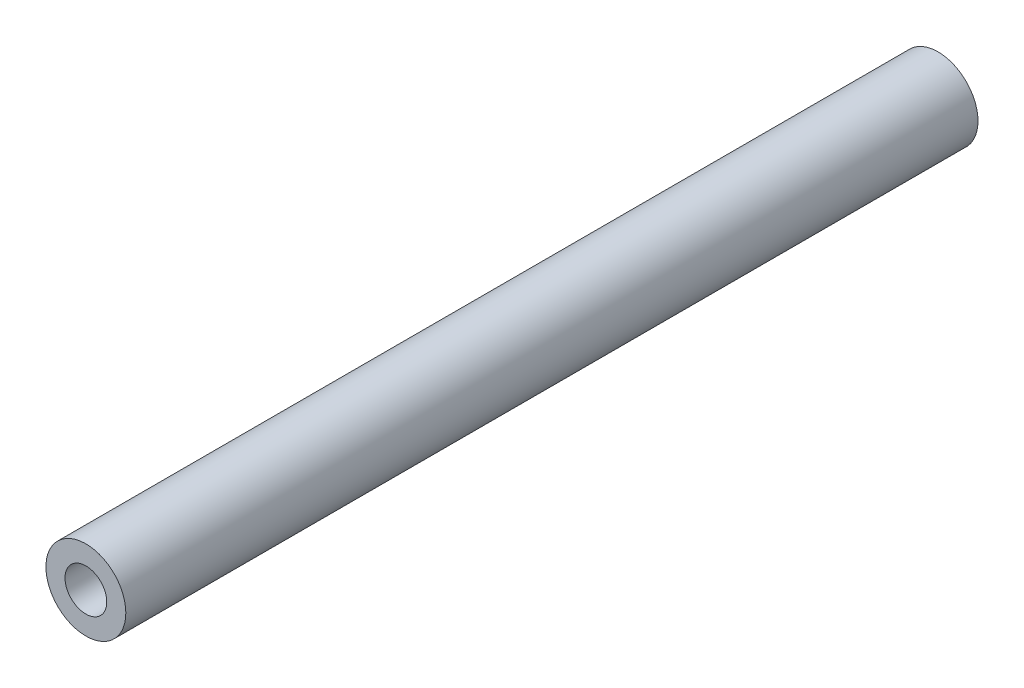
SolidWorks part; units mm, degrees
material "6061-T6 (SS)"
ref_plane "Front Plane" through (0, 0, 0) normal (0, 0, 1) x (1, 0, 0)
ref_plane "Top Plane" through (0, 0, 0) normal (0, 1, 0) x (1, 0, 0)
ref_plane "Right Plane" through (0, 0, 0) normal (1, 0, 0) x (0, 0, -1)
sketch "Sketch1" plane through (0, 0, 0) normal (0, 0, 1) x (1, 0, 0)
  circle A0 centre (0, 0) radius 4.7625
  circle A1 centre (0, 0) radius 2.4892
  dimension "D1" = 4.9784
  dimension "D2" = 9.525
extrude "Boss-Extrude1" add sketch "Sketch1" along normal blind 101.6
